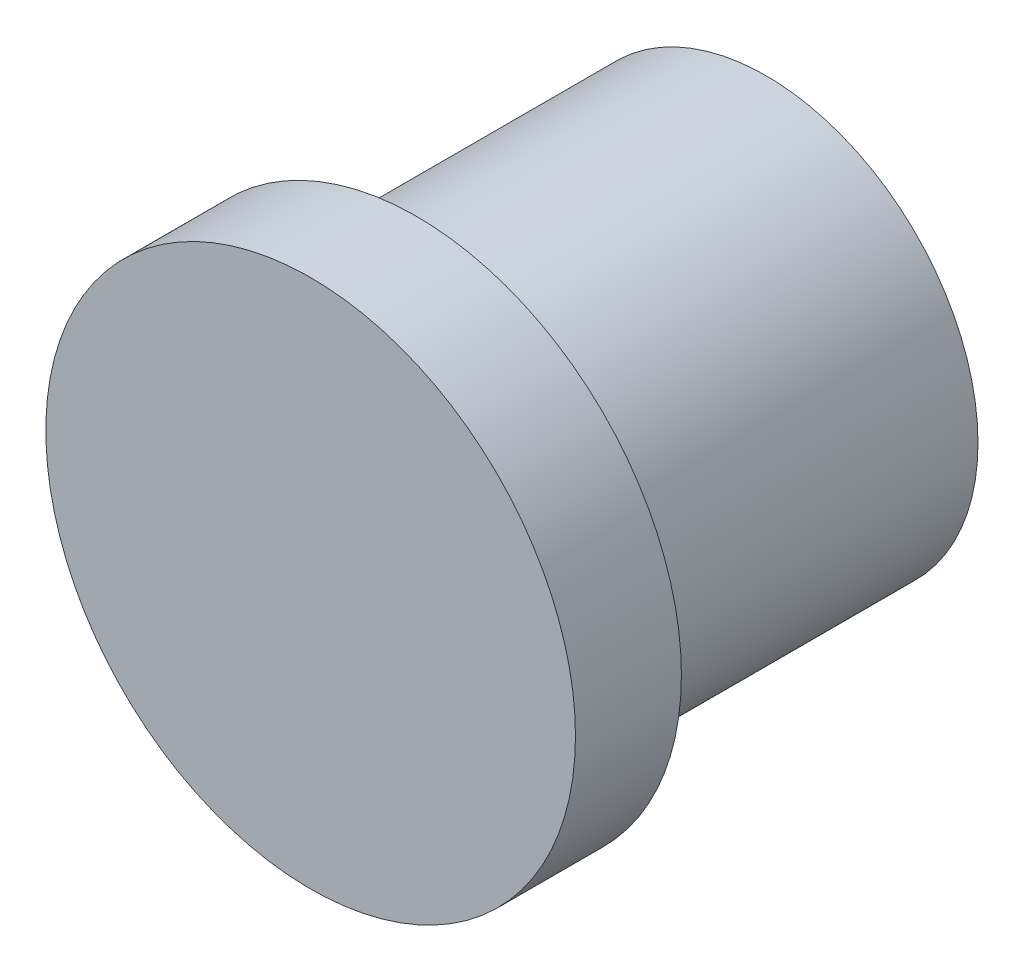
SolidWorks part; units mm, degrees
material "AISI 1020 Acero laminado en frío"
ref_plane "Alzado" through (0, 0, 0) normal (0, 0, 1) x (1, 0, 0)
ref_plane "Planta" through (0, 0, 0) normal (0, 1, 0) x (1, 0, 0)
ref_plane "Vista lateral" through (0, 0, 0) normal (1, 0, 0) x (0, 0, -1)
sketch "Croquis1" plane through (0, 0, 0) normal (0, 0, 1) x (1, 0, 0)
  circle A0 centre (0, 0) radius 20
  dimension "D1" = 40
extrude "Saliente-Extruir2" add sketch "Croquis1" along normal mid plane 43
sketch "Croquis3" plane through (0, 0, 21.5) normal (0, 0, 1) x (1, 0, 0)
  circle A1 centre (0, 0) radius 20
  circle A2 centre (0, 0) radius 20
  circle A4 centre (0, 0) radius 25
  circle A5 centre (0, 0) radius 25
  dimension "D1" = 0
  dimension "D2" = 5
extrude "Saliente-Extruir3" add sketch "Croquis3" against normal blind 10
